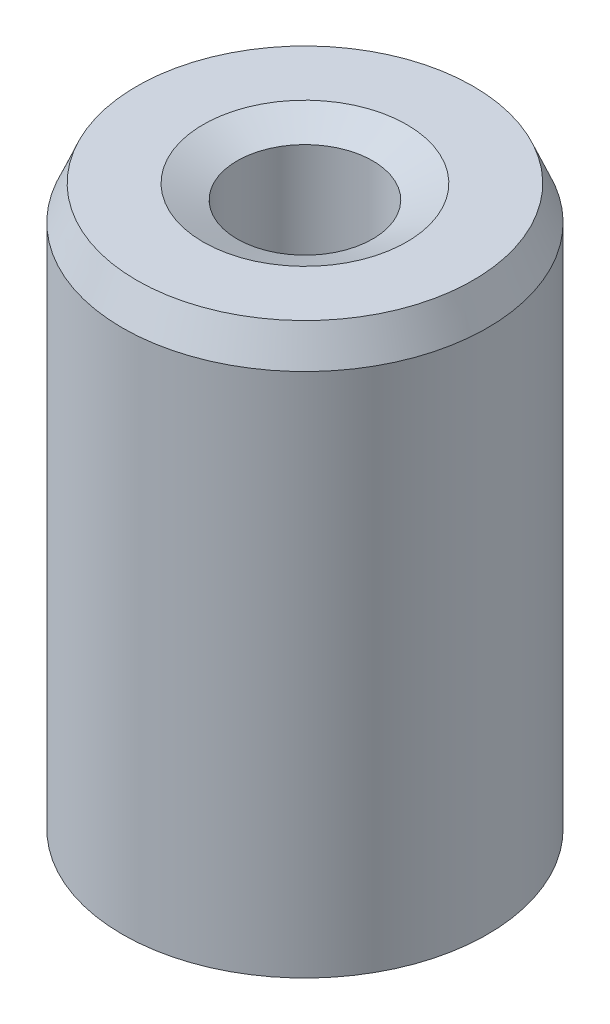
SolidWorks part; units mm, degrees
ref_plane "Front Plane" through (0, 0, 0) normal (0, 0, 1) x (1, 0, 0)
ref_plane "Top Plane" through (0, 0, 0) normal (0, 1, 0) x (1, 0, 0)
ref_plane "Right Plane" through (0, 0, 0) normal (1, 0, 0) x (0, 0, -1)
sketch "Sketch1" plane through (0, 0, 0) normal (0, 1, 0) x (1, 0, 0)
  circle A0 centre (0, 0) radius 5
  dimension "SLEEVE_OD" = 10
extrude "Boss-Extrude1" add sketch "Sketch1" along normal blind 15.7118
sketch "Sketch2" plane through (0, 0, 0) normal (0, 1, 0) x (1, 0, 0)
  circle A0 centre (0, 0) radius 1.8563
  dimension "BORE_D" = 3.7127
extrude "Cut-Extrude1" cut sketch "Sketch2" along normal through all
chamfer "Chamfer1" distance 0.9312 angle 22.939 4 edges at (0, 15.7118, 1.8563) (0, 0, 1.8563) (0, 0, 5) (0, 15.7118, 5) first distance on face at (0, 15.7118, 1.8563) first distance on face at (0, 0, 1.8563) first distance on face at (0, 15.7118, 5)
